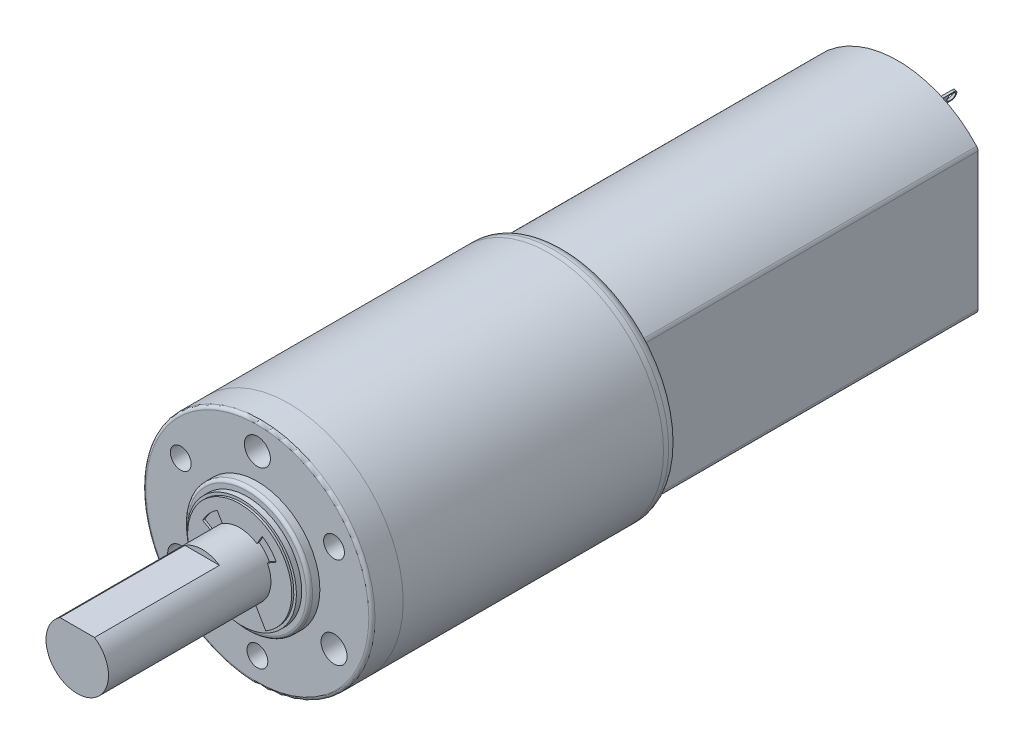
SolidWorks part; units mm, degrees
material "AISI 1035 鋼 (SS)"
ref_plane "前基準面" through (0, 0, 0) normal (0, 0, 1) x (1, 0, 0)
ref_plane "上基準面" through (0, 0, 0) normal (0, 1, 0) x (1, 0, 0)
ref_plane "右基準面" through (0, 0, 0) normal (1, 0, 0) x (0, 0, -1)
sketch "草圖1" plane through (0, 0, 0) normal (0, 0, 1) x (1, 0, 0)
  circle A0 centre (0, 0) radius 10.25
  dimension "D1" = 20.5
extrude "填料-伸長1" add sketch "草圖1" along normal blind 32
sketch "草圖2" plane through (0, 0, 32) normal (0, 0, 1) x (1, 0, 0)
  line L0 (-7.7, 6.7655) -> (-7.7, -6.7655)
  line L1 (7.7, -6.7655) -> (7.7, 6.7655)
  circle A0 centre (0, 0) radius 10.25 construction
  arc A1 (7.7, 6.7655) -> (7.7, -6.7655) centre (0, 0) cw
  circle M3 centre (0, 0) radius 10.25
  dimension "D1" = 15.4
extrude "除料-伸長1" cut sketch "草圖2" against normal through all and the other way through all contours L0 M3 | L1 M3 region at (-8.7317, 0, 32) region at (8.7317, 0, 32)
sketch "草圖3" plane through (0, 0, 32) normal (0, 0, 1) x (1, 0, 0)
  circle A0 centre (0, 0) radius 11
  dimension "D1" = 22
extrude "填料-伸長2" add sketch "草圖3" along normal blind 1.5
sketch "草圖4" plane through (0, 0, 33.5) normal (0, 0, 1) x (1, 0, 0)
  circle A1 centre (0, 0) radius 11
  circle A2 centre (0, 0) radius 11
  dimension "D1" = 0
extrude "填料-伸長3" add sketch "草圖4" along normal blind 25 separate body
sketch "草圖5" plane through (0, 0, 58.5) normal (0, 0, 1) x (1, 0, 0)
  circle A1 centre (0, 0) radius 11
  circle A2 centre (0, 0) radius 11
  dimension "D1" = 0
extrude "填料-伸長4" add sketch "草圖5" along normal blind 3 separate body
sketch "草圖6" plane through (0, 0, 61.5) normal (0, 0, 1) x (1, 0, 0)
  circle A0 centre (0, 0) radius 6
  dimension "D1" = 12
extrude "填料-伸長5" add sketch "草圖6" along normal blind 1
fillet "圓角1" radius 1 1 edges at (11, 0, 32)
fillet "圓角2" radius 0.3 2 edges at (11, 0, 61.5) (6, 0, 62.5)
fillet "圓角3" radius 0.5 4 edges at (-7.7, 6.7655, 16.0159) (-7.7, -6.7655, 16.0159) (7.7, -6.7655, 16.0159) (7.7, 6.7655, 16.0159)
sketch "草圖7" plane through (0, 0, 62.5) normal (0, 0, 1) x (1, 0, 0)
  circle A0 centre (0, 0) radius 5.25
  dimension "D1" = 10.5
extrude "填料-伸長6" add sketch "草圖7" along normal blind 0.5
sketch "草圖8" plane through (0, 0, 63) normal (0, 0, 1) x (1, 0, 0)
  circle A0 centre (0, 0) radius 3
  dimension "D1" = 6
extrude "填料-伸長7" add sketch "草圖8" along normal blind 15.8
sketch "草圖9" plane through (0, 0, 78.8) normal (0, 0, 1) x (1, 0, 0)
  line L0 (-1.6583, 2.5) -> (1.6583, 2.5)
  circle A0 centre (0, 0) radius 3 construction
  circle A1 centre (0, 0) radius 3 construction
  arc A2 (-1.6583, 2.5) -> (1.6583, 2.5) centre (0, 0) cw
  circle M3 centre (0, 0) radius 3
  dimension "D1" = 2.5
extrude "除料-伸長2" cut sketch "草圖9" against normal blind 12 contours L0 M3 region at (0, 2.7015, 78.8)
sketch "草圖10" plane through (0, 0, 63) normal (0, 0, 1) x (1, 0, 0)
  line L0 (-2.5, -4.3301) -> (-1.5, -2.5981)
  line L1 (2.5, -4.3301) -> (1.4996, -2.5974)
  line L2 (0, 0) -> (0, -3) construction
  line L3 (-2.6861, 1.3359) -> (-3.5522, 1.8359)
  line L4 (-1.6583, 2.5) -> (-2.1583, 3.366)
  line L5 (1.6583, 2.5) -> (2.1583, 3.366)
  line L6 (2.656, 1.3931) -> (3.522, 1.8931)
  line L7 (0, 0) -> (0, 3) construction
  arc A1 (-1.6583, 2.5) -> (1.6583, 2.5) centre (0, 0) ccw construction
  arc A2 (-2.5, -4.3301) -> (2.5, -4.3301) centre (0, 0) cw
  arc A3 (-1.5, -2.5981) -> (-2.6861, 1.3359) centre (0, 0) cw
  arc A4 (1.4996, -2.5974) -> (2.656, 1.3931) centre (0, 0) ccw
  arc A5 (1.6583, 2.5) -> (-1.6583, 2.5) centre (0, 0) ccw
  arc A6 (1.6583, 2.5) -> (-1.6583, 2.5) centre (0, 0) ccw construction
  arc A7 (-3.5522, 1.8359) -> (-2.1583, 3.366) centre (0, 0) cw
  arc A8 (3.522, 1.8931) -> (2.1583, 3.366) centre (0, 0) ccw
  dimension "D1" = 5
  dimension "D4" = 90
  dimension "D5" = 90
  dimension "D2" = 60
  dimension "D3" = 2
  dimension "D6" = 2.0008
  dimension "D7" = 1
  dimension "D8" = 30
  dimension "D9" = 30
extrude "填料-伸長8" add sketch "草圖10" along normal blind 0.2 contours L6 A8 L5 A5 L4 A7 L3 A3 L0 A2 L1 A4
hole_wizard "M3x0.5 螺紋孔1" positions "草圖13" profile "草圖14" tap size "M3x0.5" standard "Ansi Metric"
sketch "草圖13" plane through (0, 0, 61.5) normal (0, 0, 1) x (1, 0, 0)
  circle A1 centre (0, 0) radius 8.5 construction
  point P8 (0, 8.5)
  dimension "D1" = 17
sketch "草圖14" plane through (0, 8.5, 61.5) normal (1, 0, 0) x (0, -1, 0)
  line L0 (0, 0) -> (0, 4.7511)
  line L1 (0, 4.7511) -> (1.25, 4)
  line L2 (1.25, 4) -> (1.25, 0)
  line L5 (1.25, 0) -> (0, 0)
  line L10 (0, 4.7511) -> (-1.25, 4) construction
  line L11 (0, -6.35) -> (0, 107.95) construction
  dimension "螺孔鑽直徑" = 2.5
  dimension "螺孔鑽深度" = 4
  dimension "導頭角度" = 118
pattern_circular "環狀複製排列1" count 3 over 360 about axis through (0, 0, 61.5) along (0, 0, -1) of "M3x0.5 螺紋孔1" reverse direction yes
sketch "草圖15" plane through (0, 0, 61.5) normal (0, 0, 1) x (1, 0, 0)
  circle A0 centre (0, 0) radius 8.5 construction
  circle A1 centre (0, -8.5) radius 1
  dimension "D1" = 2
extrude "除料-伸長3" cut sketch "草圖15" against normal blind 2
pattern_circular "環狀複製排列2" count 3 over 360 about axis through (0, 0, 61.5) along (0, 0, -1) of "除料-伸長3" reverse direction yes
sketch "草圖23" plane through (0, 0, 0) normal (0, 0, -1) x (-1, 0, 0)
  line L0 (-7.6662, 6.7552) -> (7.6662, -6.7552) construction
  line L1 (7.6662, 6.7552) -> (-7.6662, -6.7552) construction
  line L2 (-7.375, 6.4986) -> (-7.375, -6.4986)
  line L3 (7.375, -6.4986) -> (7.375, 6.4986)
  arc A0 (-7.5692, 6.9115) -> (-7.7, 6.5744) centre (-7.2, 6.5744) ccw construction
  arc A1 (7.5692, -6.9115) -> (7.7, -6.5744) centre (7.2, -6.5744) ccw construction
  arc A2 (7.7, 6.5744) -> (7.5692, 6.9115) centre (7.2, 6.5744) ccw construction
  arc A3 (-7.7, -6.5744) -> (-7.5692, -6.9115) centre (-7.2, -6.5744) ccw construction
  arc A4 (-7.375, 6.4986) -> (7.375, 6.4986) centre (0, 0) cw
  arc A5 (-7.375, -6.4986) -> (7.375, -6.4986) centre (0, 0) ccw
  dimension "D1" = 14.75
extrude "除料-伸長4" cut sketch "草圖23" against normal blind 1 contours L2 A5 L3 A4 region at (0, 0, 0)
sketch "草圖24" plane through (0, 0, 1) normal (0, 0, -1) x (-1, 0, 0)
  circle A0 centre (0, 0) radius 4
  dimension "D1" = 8
extrude "填料-伸長9" add sketch "草圖24" along normal blind 3
sketch "草圖25" plane through (0, 0, -2) normal (0, 0, -1) x (-1, 0, 0)
  circle A0 centre (0, 0) radius 1
  dimension "D1" = 2
extrude "填料-伸長10" add sketch "草圖25" along normal blind 1
fillet "圓角4" radius 0.25 1 edges at (-4, 0, -2)
fillet "圓角5" radius 0.1 1 edges at (-1, 0, -3)
sketch "草圖26" plane through (0, 0, 1) normal (0, 0, -1) x (-1, 0, 0)
  line L0 (0, 0) -> (0, 9.8297) construction
  line L1 (0, 0) -> (-3.362, 9.2369) construction
  circle A0 centre (-2.7362, 7.5175) radius 0.75
  arc A1 (7.375, 6.4986) -> (-7.375, 6.4986) centre (0, 0) ccw construction
  arc A2 (7.375, 6.4986) -> (-7.375, 6.4986) centre (0, 0) ccw construction
  dimension "D2" = 1.5
  dimension "D1" = 20
  dimension "D3" = 8
extrude "填料-伸長11" add sketch "草圖26" along normal blind 0.3
sketch "草圖27" plane through (0, 0, 0.7) normal (0, 0, -1) x (-1, 0, 0)
  line L0 (0, 0) -> (0, 9.8297) construction
  line L1 (-3.0011, 7.9532) -> (-2.6591, 7.0135)
  line L2 (-3.0011, 7.9532) -> (-2.8132, 8.0216)
  line L3 (-2.6591, 7.0135) -> (-2.4712, 7.0819)
  line L4 (-2.8132, 8.0216) -> (-2.4712, 7.0819)
  line L5 (-3.0011, 7.9532) -> (-2.4712, 7.0819) construction
  line L6 (-2.6591, 7.0135) -> (-2.8132, 8.0216) construction
  arc A0 (7.375, 6.4986) -> (-7.375, 6.4986) centre (0, 0) ccw construction
  circle A2 centre (-2.7362, 7.5175) radius 0.75 construction
  point P6 (-2.7362, 7.5175)
  dimension "D1" = 20
  dimension "D2" = 1
  dimension "D3" = 0.2
extrude "填料-伸長12" add sketch "草圖27" along normal blind 3.5
sketch "草圖28" plane through (0.094, -0.0342, 0) normal (0.9397, -0.342, 0) x (0, 0, -1)
  line L0 (2.8, 8) -> (-0.7, 8) construction
  line L1 (2.8, 8.5) -> (2.8, 7.5) construction
  line L2 (-0.7, 8.5) -> (-0.7, 7.5) construction
  circle A0 centre (2.3, 8) radius 0.4
  dimension "D1" = 0.5
  dimension "D2" = 0.8
extrude "除料-伸長5" cut sketch "草圖28" against normal through all
fillet "圓角6" radius 0.4 2 edges at (2.5652, 7.0477, -2.8) (2.9072, 7.9874, -2.8)
pattern_circular "環狀複製排列7" count 2 over 360 about axis through (0, 0, -2) along (0, 0, 1) of "填料-伸長12", "除料-伸長5", "填料-伸長11", "圓角6"
